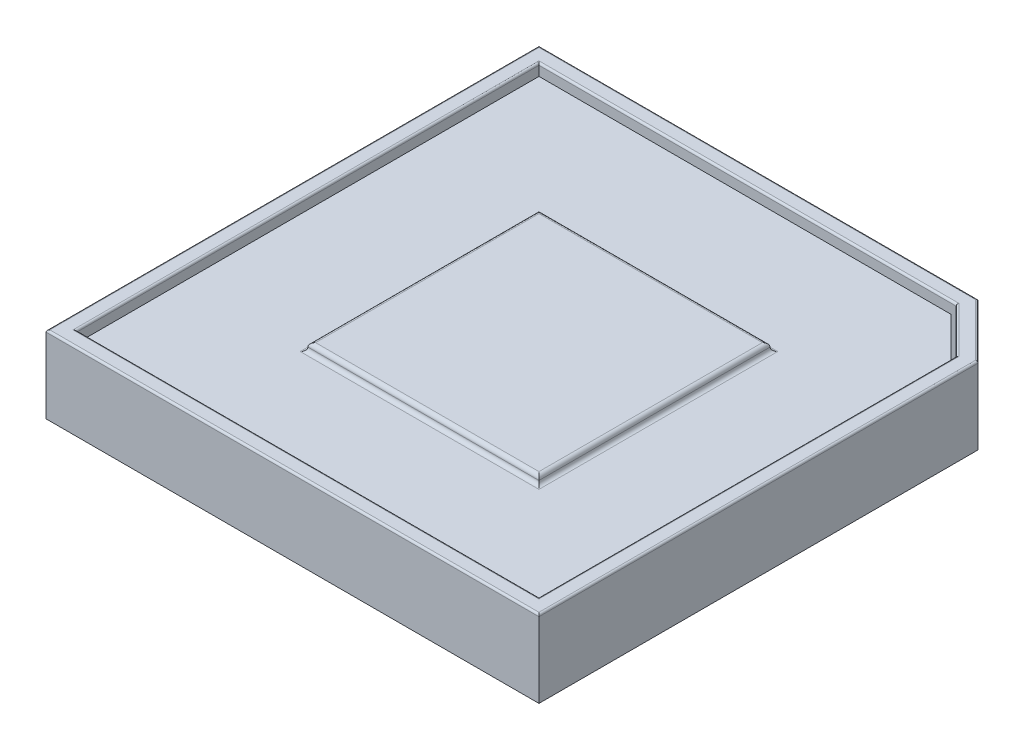
SolidWorks part; units mm, degrees
ref_plane "Front Plane" through (0, 0, 0) normal (0, 0, 1) x (1, 0, 0)
ref_plane "Top Plane" through (0, 0, 0) normal (0, 1, 0) x (1, 0, 0)
ref_plane "Right Plane" through (0, 0, 0) normal (1, 0, 0) x (0, 0, -1)
sketch "Sketch1" plane through (0, 0, 0) normal (0, 1, 0) x (1, 0, 0)
  line L0 (0, 16.256) -> (3.556, 12.7)
  line L1 (-28.956, 16.256) -> (0, 16.256)
  line L2 (-28.956, 16.256) -> (-28.956, -16.256)
  line L3 (-28.956, -16.256) -> (3.556, -16.256)
  line L4 (3.556, 12.7) -> (3.556, -16.256)
  point P3 (3.556, 16.256)
  dimension "D1" = 32.512
  dimension "D2" = 32.512
  dimension "D3" = 16.256
  dimension "D4" = 3.556
extrude "Base-Extrude" add sketch "Sketch1" along normal blind 5.08
sketch "Sketch2" plane through (0, 5.08, 0) normal (0, 1, 0) x (-1, 0, 0)
  line L10 (27.94, -15.24) -> (27.94, 15.24)
  line L11 (27.94, 15.24) -> (-2.54, 15.24)
  line L12 (-2.54, 15.24) -> (-2.54, -12.2792)
  line L13 (-2.54, -12.2792) -> (0.4208, -15.24)
  line L14 (0.4208, -15.24) -> (27.94, -15.24)
  line L15 (27.94, -15.24) -> (27.94, 15.24)
  line L16 (27.94, 15.24) -> (-2.54, 15.24)
  line L17 (-2.54, 15.24) -> (-2.54, -12.2792)
  line L18 (-2.54, -12.2792) -> (0.4208, -15.24)
  line L19 (0.4208, -15.24) -> (27.94, -15.24)
  dimension "D1" = 1.016
extrude "Cut-Extrude1" cut sketch "Sketch2" against normal blind 4.064
sketch "Sketch3" plane through (0, 1.016, 0) normal (0, 1, 0) x (-1, 0, 0)
  line L10 (0.5261, -14.986) -> (27.686, -14.986)
  line L11 (27.686, -14.986) -> (27.686, 14.986)
  line L12 (27.686, 14.986) -> (-2.286, 14.986)
  line L13 (-2.286, 14.986) -> (-2.286, -12.1739)
  line L14 (-2.286, -12.1739) -> (0.5261, -14.986)
  line L15 (0.5261, -14.986) -> (27.686, -14.986)
  line L16 (27.686, -14.986) -> (27.686, 14.986)
  line L17 (27.686, 14.986) -> (-2.286, 14.986)
  line L18 (-2.286, 14.986) -> (-2.286, -12.1739)
  line L19 (-2.286, -12.1739) -> (0.5261, -14.986)
  dimension "D1" = 0.254
extrude "Boss-Extrude1" add sketch "Sketch3" along normal blind 3.556
sketch "Sketch4" plane through (0, 4.572, 0) normal (0, 1, 0) x (-1, 0, 0)
  line L0 (-3.556, 16.256) -> (28.956, -16.256) construction
  line L1 (4.3519, -6.8919) -> (19.5919, -6.8919)
  line L2 (4.3519, -6.8919) -> (4.3519, 8.3481)
  line L3 (4.3519, 8.3481) -> (19.5919, 8.3481)
  line L4 (19.5919, -6.8919) -> (19.5919, 8.3481)
  dimension "D1" = 15.24
extrude "Boss-Extrude2" add sketch "Sketch4" along normal blind 0.508
fillet "Fillet2" radius 0.127 10 edges at (-14.478, 5.08, -16.256) (1.778, 5.08, -14.478) (3.556, 5.08, 1.778) (-12.7, 5.08, 16.256) (-28.956, 5.08, 0) (-27.94, 5.08, 0) (-12.7, 5.08, 15.24) (2.54, 5.08, 1.4804) (1.0596, 5.08, -13.7596) (-14.1804, 5.08, -15.24)
fillet "Fillet3" radius 0.254 8 edges at (-11.9719, 5.08, 8.3481) (-19.5919, 5.08, 0.7281) (-11.9719, 5.08, -6.8919) (-4.3519, 5.08, 0.7281) (-11.9719, 4.572, -6.8919) (-19.5919, 4.572, 0.7281) (-4.3519, 4.572, 0.7281) (-11.9719, 4.572, 8.3481)
sketch "Sketch5" plane through (0, 0, 0) normal (0, -1, 0) x (1, 0, 0)
  line L0 (0, -16.256) -> (-28.956, -16.256) construction
  circle A0 centre (0, -10.541) radius 0.3556
  dimension "D1" = 0.7112
  dimension "D2" = 5.715
extrude "Boss-Extrude3" add sketch "Sketch5" along normal blind 2.54
pattern_linear "LPattern1" count 10 spacing 2.54 along (0, 0, 1) count 11 spacing 2.54 along (-1, 0, 0) skipping (1, 2), (1, 3), (1, 4), (1, 5), (1, 6), (1, 7), (1, 8), (2, 2), (2, 3), (2, 4), (2, 5), (2, 6), (2, 7), (2, 8), (3, 2), (3, 3), (3, 4), (3, 5), (3, 6), (3, 7), (3, 8), (4, 2), (4, 3), (4, 4), (4, 5), (4, 6), (4, 7), (4, 8), (5, 2), (5, 3), (5, 4), (5, 5), (5, 6), (5, 7), (5, 8), (6, 2), (6, 3), (6, 4), (6, 5), (6, 6), (6, 7), (6, 8), (7, 2), (7, 3), (7, 4), (7, 5), (7, 6), (7, 7), (7, 8), (9, 0), (9, 10) of "Boss-Extrude3"
pattern_linear "LPattern2" count 2 spacing 2.54 along (0, 0, -1) count 11 spacing 2.54 along (-1, 0, 0) skipping (1, 0), (1, 10) of "Boss-Extrude3"
ref_plane "Board Plane" through (0, -0.254, 0) normal (0, 1, 0) x (-1, 0, 0)
sketch "Component_Outline" plane through (0, -0.254, 0) normal (0, 1, 0) x (-1, 0, 0)
  line L0 (0, -16.256) -> (28.956, -16.256) construction
  line L1 (28.956, 16.256) -> (-3.556, 16.256)
  line L2 (28.956, 16.256) -> (28.956, -16.256)
  line L3 (28.956, -16.256) -> (0, -16.256)
  line L4 (-3.556, 16.256) -> (-3.556, -12.7)
  line L5 (-3.556, 16.256) -> (-3.556, -12.7) construction
  line L6 (-3.556, -12.7) -> (0, -16.256)
